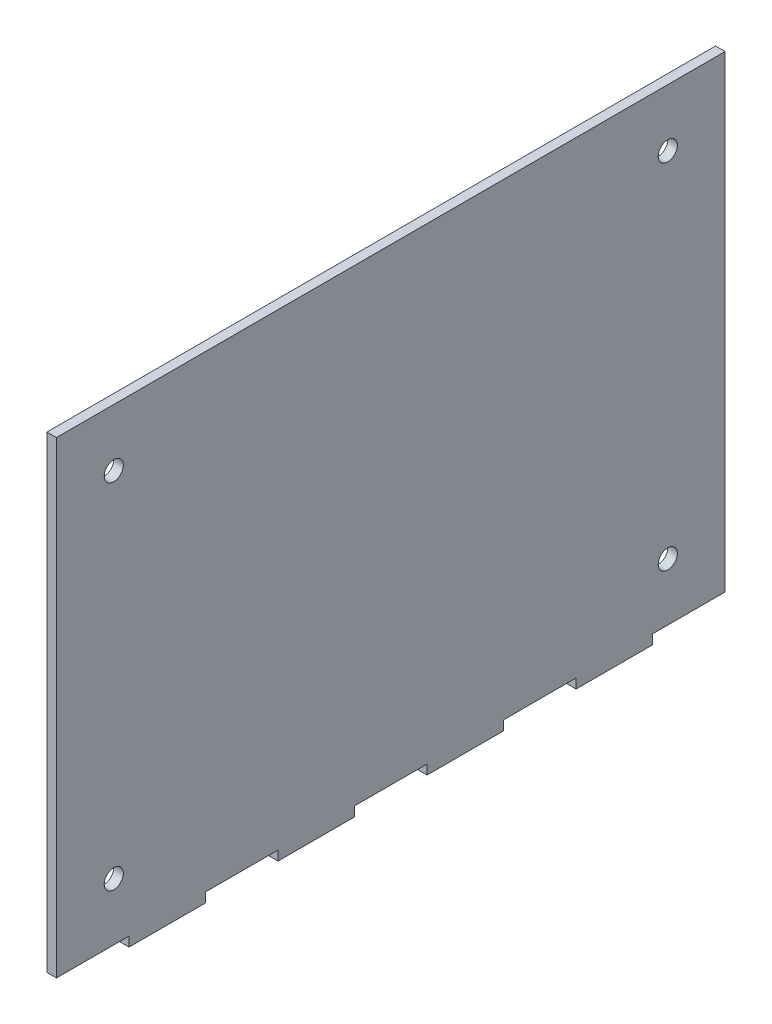
SolidWorks part; units mm, degrees
ref_plane "Front" through (0, 0, 0) normal (0, 0, 1) x (1, 0, 0)
ref_plane "Top" through (0, 0, 0) normal (0, 1, 0) x (1, 0, 0)
ref_plane "Right" through (0, 0, 0) normal (1, 0, 0) x (0, 0, -1)
sketch "Skizze1" plane through (0, 0, 0) normal (1, 0, 0) x (0, 0, -1)
  line L0 (175, 0) -> (-175, 0)
  line L1 (-175, 0) -> (-175, 250)
  line L2 (-175, 250) -> (175, 250)
  line L3 (0, 250) -> (0, 0) construction
  line L4 (175, 0) -> (175, 250)
  dimension "D1" = 350
  dimension "D2" = 250
extrude "Grundplatte" add sketch "Skizze1" along normal blind 5
sketch "Skizze2" plane through (5, 0, 0) normal (1, 0, 0) x (0, 0, -1)
  line L5 (-175, 0) -> (175, 0) construction
  line L11 (-175, 0) -> (-137, 0)
  line L12 (-175, 0) -> (-175, 5)
  line L13 (-175, 5) -> (-137, 5)
  line L14 (0, 0) -> (0, 250) construction
  line L15 (175, 250) -> (-175, 250) construction
  line L16 (-137, 0) -> (-137, 5)
  line L17 (-97, 0) -> (-59, 0)
  line L26 (-97, 0) -> (-97, 5)
  line L27 (-97, 5) -> (-59, 5)
  line L28 (-59, 0) -> (-59, 5)
  line L29 (-137, 5) -> (-97, 5) construction
  line L30 (-59, 5) -> (-19, 5) construction
  line L31 (19, 0) -> (-19, 0)
  line L32 (-19, 0) -> (-19, 5)
  line L34 (19, 0) -> (19, 5)
  line L35 (59, 5) -> (19, 5) construction
  line L36 (137, 5) -> (97, 5) construction
  line L37 (59, 0) -> (59, 5)
  line L38 (97, 5) -> (59, 5)
  line L39 (97, 0) -> (97, 5)
  line L40 (97, 0) -> (59, 0)
  line L41 (137, 0) -> (137, 5)
  line L42 (175, 5) -> (137, 5)
  line L43 (175, 0) -> (175, 5)
  line L44 (175, 0) -> (137, 0)
  line L45 (-19, 5) -> (0, 5) construction
  line L46 (-19, 5) -> (19, 5)
  point P14 (0, 7.2519)
  dimension "D1" = 40
  dimension "D2" = 5
extrude "Zapfen Boden" cut sketch "Skizze2" against normal through all
sketch "Skizze3" plane through (5, 0, 0) normal (1, 0, 0) x (0, 0, -1)
  line L0 (175, 5) -> (175, 250) construction
  line L1 (175, 250) -> (-175, 250) construction
  line L2 (0, 250) -> (0, 0) construction
  line L3 (-175, 127.5) -> (175, 127.5) construction
  line L4 (-175, 250) -> (-175, 5) construction
  circle A0 centre (145, 220) radius 5
  circle A1 centre (-145, 220) radius 5
  circle A2 centre (-145, 35) radius 5
  circle A3 centre (145, 35) radius 5
  dimension "D1" = 10
  dimension "D2" = 30
  dimension "D3" = 30
extrude "Verbindungsbohrungen" cut sketch "Skizze3" against normal through all
sketch "Skizze4" plane through (5, 0, 0) normal (1, 0, 0) x (0, 0, -1)
  line L0 (175, 127.5) -> (-175, 127.5) construction
  line L1 (175, 5) -> (175, 250) construction
  line L2 (-175, 250) -> (-175, 5) construction
  line L3 (170, 177.5) -> (170, 77.5)
  line L28 (175, 5) -> (170, 5)
  line L29 (175, 5) -> (175, 37.5)
  line L30 (175, 37.5) -> (170, 37.5)
  line L31 (170, 5) -> (170, 37.5)
  line L32 (170, 77.5) -> (175, 77.5)
  line L33 (175, 5) -> (175, 250) construction
  line L34 (175, 77.5) -> (175, 177.5)
  line L35 (170, 177.5) -> (175, 177.5)
  line L36 (170, 250) -> (170, 217.5)
  line L37 (175, 217.5) -> (170, 217.5)
  line L38 (175, 250) -> (175, 217.5)
  line L39 (175, 250) -> (170, 250)
  point P18 (170, 127.5)
  dimension "D1" = 5
  dimension "D2" = 40
  dimension "D3" = 100
extrude "Zapfen Seite" [suppressed] cut sketch "Skizze4" against normal through all
sketch "Skizze5" [suppressed] plane through (0, 0, 0) normal (-1, 0, 0) x (0, 0, 1)
  line L0 (0, 300) -> (0, 0) construction
  line L1 (-200, 300) -> (200, 300) construction
  line L2 (-200, 5) -> (-152, 5) construction
  line L3 (-200, 300) -> (-195, 300)
  line L4 (-200, 300) -> (-200, 5)
  line L5 (-200, 5) -> (-195, 5)
  line L6 (-195, 300) -> (-195, 5)
  dimension "D1" = 5
extrude "5mm Wandstärke Entfernnung" [suppressed] cut sketch "Skizze5" against normal through all
sketch "Skizze7" [suppressed] plane through (0, 0, 0) normal (-1, 0, 0) x (0, 0, 1)
  line L0 (-195, 5) -> (-195, 300) construction
  line L1 (-195, 300) -> (-200, 300)
  line L2 (-195, 300) -> (-195, 242.5)
  line L3 (-195, 242.5) -> (-200, 242.5)
  line L4 (-200, 300) -> (-200, 242.5)
  line L5 (-195, 202.5) -> (-200, 202.5)
  line L6 (-195, 202.5) -> (-195, 102.5)
  line L7 (-195, 102.5) -> (-200, 102.5)
  line L8 (-200, 202.5) -> (-200, 102.5)
  line L9 (-200, 152.5) -> (200, 152.5) construction
  line L10 (-195, 5) -> (-200, 5)
  line L11 (-195, 5) -> (-195, 62.5)
  line L12 (-195, 62.5) -> (-200, 62.5)
  line L13 (-200, 5) -> (-200, 62.5)
  line L14 (200, 300) -> (200, 5) construction
  dimension "D1" = 5
  dimension "D2" = 40
  dimension "D3" = 100
extrude "Aufsatz-Linear austragen2" [suppressed] add sketch "Skizze7" against normal up to surface (5 mm away) up to face at (5, 35, -140)
